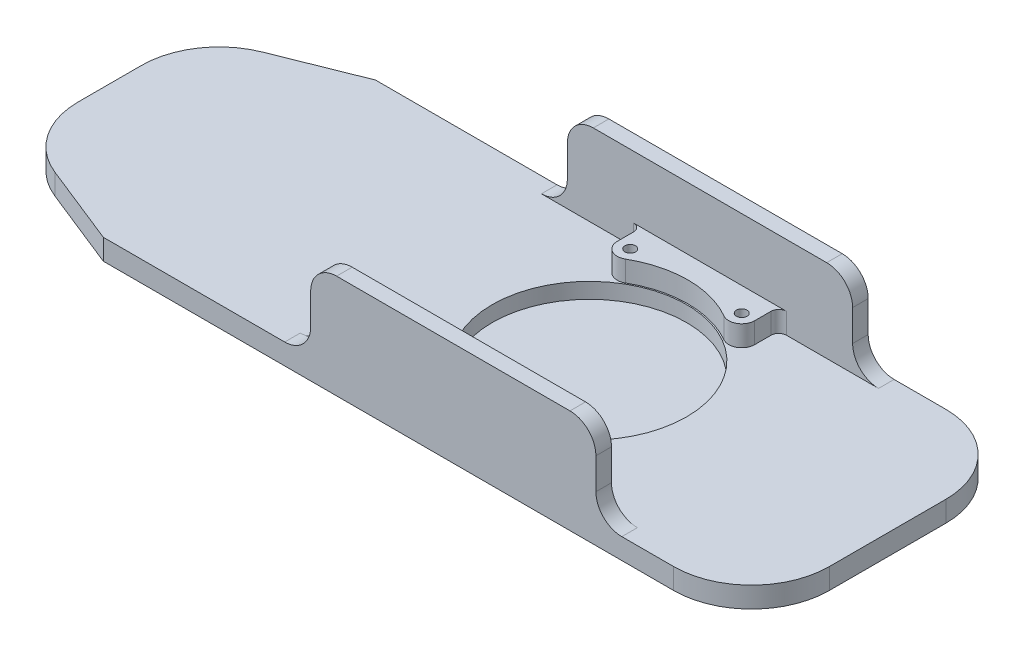
SolidWorks part; units mm, degrees
ref_plane "前视基准面" through (0, 0, 0) normal (0, 0, 1) x (1, 0, 0)
ref_plane "上视基准面" through (0, 0, 0) normal (0, 1, 0) x (1, 0, 0)
ref_plane "右视基准面" through (0, 0, 0) normal (1, 0, 0) x (0, 0, -1)
sketch "草图1" plane through (0, 0, 0) normal (0, 0, 1) x (1, 0, 0)
  line L0 (0, 0) -> (300, 0)
  line L1 (300, 0) -> (300, 40)
  line L2 (300, 40) -> (130, 40)
  line L3 (130, 40) -> (0, 8)
  line L4 (0, 8) -> (0, 0)
  dimension "D1" = 300
  dimension "D2" = 40
  dimension "D3" = 170
  dimension "D4" = 8
extrude "凸台-拉伸1" add sketch "草图1" along normal mid plane 105
sketch "草图3" plane through (0, 40, 0) normal (0, 1, 0) x (1, 0, 0)
  line L0 (300, -52.5) -> (130, -52.5) construction
  line L1 (300, 52.5) -> (240, 52.5)
  line L2 (300, 52.5) -> (300, -52.5)
  line L3 (300, -52.5) -> (240, -52.5)
  line L4 (240, 52.5) -> (240, -52.5)
  dimension "D1" = 60
extrude "切除-拉伸1" cut sketch "草图3" against normal offset from surface (32 mm away) 8 up to face at (150, 0, 0)
ref_plane "基准面4" through (0, 0, 30) normal (0, 0, 1) x (1, 0, 0)
sketch "草图4" plane through (0, 0, 30) normal (0, 0, 1) x (1, 0, 0)
  line L0 (300, 0) -> (300, 8) construction
  line L1 (300, 8) -> (246, 8)
  line L2 (300, 8) -> (300, 79)
  line L3 (300, 79) -> (246, 79)
  line L4 (246, 8) -> (246, 79)
  line L5 (0, 0) -> (300, 0) construction
  circle A0 centre (260, 65) radius 9.5
  dimension "D2" = 19
  dimension "D4" = 14
  dimension "D1" = 40
  dimension "D3" = 65
  dimension "D5" = 14
extrude "凸台-拉伸3" add sketch "草图4" along normal mid plane 45
extrude "切除-拉伸2" cut sketch "草图4<3>" against normal mid plane 29
sketch "草图4<3>" plane through (0, 0, 30) normal (0, 0, 1) x (1, 0, 0) same geometry as "草图4"
sketch "草图5" plane through (0, 0, 44.5) normal (0, 0, -1) x (-1, 0, 0)
  circle A0 centre (-260, 65) radius 9.5
  circle A1 centre (-260, 65) radius 8
  circle A2 centre (-260, 65) radius 9.5 construction
  dimension "D1" = 16
  dimension "D2" = 19
extrude "凸台-拉伸4" add sketch "草图5" against normal blind 2
sketch "草图6" plane through (0, 0, 15.5) normal (0, 0, 1) x (1, 0, 0)
  circle A0 centre (260, 65) radius 8
  circle A1 centre (260, 65) radius 9.5
extrude "凸台-拉伸5" add sketch "草图6" against normal blind 2
fillet "圆角1" radius 14 2 edges at (246, 79, 48.5) (246, 79, 11.5)
mirror "镜向2" about plane through (0, 0, 0) normal (0, 0, 1) of "圆角1", "凸台-拉伸3", "切除-拉伸2", "凸台-拉伸4", "凸台-拉伸5"
sketch "草图8" plane through (0, 0, 0) normal (-1, 0, 0) x (0, 0, 1)
  line L0 (52.5, 8) -> (-52.5, 8) construction
  line L1 (-47.5, 8) -> (47.5, 8)
  line L2 (-47.5, 8) -> (-47.5, 86.9311)
  line L3 (-47.5, 86.9311) -> (47.5, 86.9311)
  line L4 (47.5, 8) -> (47.5, 86.9311)
  line L5 (52.5, 40) -> (52.5, 8) construction
  line L6 (-52.5, 40) -> (-52.5, 8) construction
  dimension "D1" = 5
  dimension "D2" = 5
extrude "切除-拉伸4" cut sketch "草图8" against normal blind 130
sketch "草图7" plane through (0, 0, 0) normal (1, 0, 0) x (0, 0, -1)
  circle A0 centre (0, 65) radius 11
  dimension "D1" = 22
  dimension "D2" = 65
extrude "切除-拉伸3" [suppressed] cut sketch "草图7" along normal up to surface (240 mm away)
sketch "草图10" plane through (0, 40, 0) normal (0, 1, 0) x (1, 0, 0)
  line L0 (130, 47.5) -> (130, -47.5) construction
  line L1 (135, 46.5) -> (235, 46.5)
  line L2 (135, 46.5) -> (135, -46.5)
  line L3 (135, -46.5) -> (235, -46.5)
  line L4 (235, 46.5) -> (235, -46.5)
  line L6 (240, -52.5) -> (130, -52.5) construction
  line L7 (240, 52.5) -> (130, 52.5) construction
  line L8 (240, 52.5) -> (240, -52.5) construction
  dimension "D1" = 5
  dimension "D2" = 5
  dimension "D3" = 6
  dimension "D4" = 6
extrude "切除-拉伸6" cut sketch "草图10" against normal up to surface (32 mm away) up to face at (65, 8, 0)
sketch "草图11" plane through (0, 0, 0) normal (0, -1, 0) x (1, 0, 0)
  line L0 (-14.6132, 52.5) -> (50.0309, 52.5)
  line L1 (130, 52.5) -> (0, 52.5) construction
  line L5 (0, -47.5) -> (0, 47.5) construction
  line L6 (0, 32.5) -> (0, -32.5)
  line L10 (130, -52.5) -> (0, -52.5) construction
  line L11 (50, -52.5) -> (-14.6132, -52.5)
  line L12 (-14.6132, -52.5) -> (-14.6132, 52.5)
  line L14 (0, 32.5) -> (50.0309, 52.5)
  line L15 (0, -32.5) -> (50, -52.5)
  line L16 (0, 52.5) -> (300, 52.5) construction
  dimension "D2" = 20
  dimension "D3" = 20
extrude "切除-拉伸7" cut sketch "草图11" against normal blind 73
sketch "草图12" plane through (0, 8, 0) normal (0, 1, 0) x (1, 0, 0)
  line L1 (50, 52.5) -> (30.577, 52.5)
  line L2 (50, 52.5) -> (50, -69.3601)
  line L3 (50, -69.3601) -> (30.577, -69.3601)
  line L4 (30.577, 52.5) -> (30.577, -69.3601)
extrude "切除-拉伸8" cut sketch "草图12" along normal blind 73
sketch "草图14" plane through (0, 0, 52.5) normal (0, 0, 1) x (1, 0, 0)
  line L0 (300, 79) -> (260, 79) construction
  line L1 (275.0754, 79) -> (318.0378, 79)
  line L2 (318.0378, 79) -> (300, 8)
  arc A0 (275.0754, 79) -> (300, 8) centre (150.7862, -4.5067) cw
extrude "切除-拉伸10" cut sketch "草图14" against normal mid plane 300
sketch "草图15" plane through (0, 8, 0) normal (0, 1, 0) x (1, 0, 0)
  line L0 (185, 0) -> (185, 27.1177) construction
  line L2 (135, 0) -> (219.6534, 0) construction
  line L3 (135, 46.5) -> (135, -46.5) construction
  line L4 (226.5348, 11.1292) -> (185, 0) construction
  line L5 (235, -46.5) -> (235, 46.5) construction
  line L6 (185, 0) -> (163.5, -37.2391) construction
  line L7 (185, 0) -> (147.7609, -21.5) construction
  circle A0 centre (185, 0) radius 43 construction
  circle A3 centre (163.5, -37.2391) radius 2.05
  circle A5 centre (185, 0) radius 43 construction
  circle A8 centre (185, 0) radius 43 construction
  circle A13 centre (163.5, 37.2391) radius 2.05
  circle A15 centre (206.5, 37.2391) radius 2.05
  circle A17 centre (206.5, -37.2391) radius 2.05
  circle A19 centre (185, 0) radius 37.5
  point P28 (185, 0)
  dimension "D2" = 150
  dimension "D3" = 86
  dimension "D7" = 75
  dimension "D8" = 4.1
  dimension "D1" = 15
  dimension "D5" = 50
  dimension "D6" = 30
  dimension "D4" = 3
extrude "切除-拉伸11" cut sketch "草图15" against normal through all
chamfer "倒角1" [suppressed] distance 2.5 angle 45
sketch "草图16" plane through (0, 0, 52.5) normal (0, 0, 1) x (1, 0, 0)
  line L0 (240, 40) -> (130, 40) construction
  line L1 (140, 40) -> (230, 40)
  line L2 (140, 40) -> (140, 25)
  line L3 (140, 25) -> (230, 25)
  line L4 (230, 40) -> (230, 25)
  dimension "D1" = 10
  dimension "D2" = 10
  dimension "D3" = 15
extrude "切除-拉伸12" [suppressed] cut sketch "草图16" against normal through all
chamfer "倒角2" [suppressed] distance 2.5 angle 45
sketch "草图18" plane through (0, 0, 52.5) normal (0, 0, 1) x (1, 0, 0)
  line L1 (246, 8) -> (307.2222, 8)
  line L2 (246, 8) -> (246, 105.8082)
  line L3 (246, 105.8082) -> (307.2222, 105.8082)
  line L4 (307.2222, 8) -> (307.2222, 105.8082)
extrude "切除-拉伸13" cut sketch "草图18" against normal blind 170
sketch "草图19" plane through (0, 0, 0) normal (0, -1, 0) x (1, 0, 0)
  circle A0 centre (185, 0) radius 37.5
extrude "凸台-拉伸6" add sketch "草图19" against normal blind 2
fillet "圆角2" radius 30 4 edges at (0, 4, -32.5) (0, 4, 32.5) (300, 4, -52.5) (300, 4, 52.5)
sketch "草图21" plane through (0, 8, 0) normal (0, 1, 0) x (1, 0, 0)
  line L1 (130, 52.5) -> (-2.1093, 52.5)
  line L2 (130, 52.5) -> (130, -73.0189)
  line L3 (130, -73.0189) -> (-2.1093, -73.0189)
  line L4 (-2.1093, 52.5) -> (-2.1093, -73.0189)
extrude "切除-拉伸15" cut sketch "草图21" along normal blind 149
hole_wizard "大小mm 暗销孔1" positions "3D草图1" profile "草图22" hole size "Ø10.0" standard "GB"
sketch3d "3D草图1"
  line L0 (163.5, 0, 37.2391) -> (163.5, 8, 37.2391) construction
  line L1 (206.5, 0, 37.2391) -> (206.5, 8, 37.2391) construction
  line L2 (206.5, 0, -37.2391) -> (206.5, 8, -37.2391) construction
  line L3 (163.5, 0, -37.2391) -> (163.5, 8, -37.2391) construction
  point P0 (163.5, 0, 37.2391)
  point P4 (206.5, 0, 37.2391)
  point P8 (206.5, 0, -37.2391)
  point P12 (163.5, 0, -37.2391)
sketch "草图22" plane through (163.5, 0, 37.2391) normal (1, 0, 0) x (0, 0, -1)
  line L0 (0, 0) -> (0, 7.0043)
  line L1 (0, 7.0043) -> (5, 4)
  line L2 (5, 4) -> (5, 0)
  line L5 (5, 0) -> (0, 0)
  line L10 (0, 7.0043) -> (-5, 4) construction
  line L11 (0, -6.35) -> (0, 107.95) construction
  dimension "孔直径" = 10
  dimension "孔深度" = 4
  dimension "导头角度" = 118
sketch "草图23" plane through (130, 0, 0) normal (-1, 0, 0) x (0, 0, 1)
  line L0 (52.5, 40) -> (-52.5, 40) construction
  line L1 (-46.5, 40) -> (46.5, 40)
  line L2 (-46.5, 40) -> (-46.5, 8)
  line L3 (-46.5, 8) -> (46.5, 8)
  line L4 (46.5, 40) -> (46.5, 8)
  line L5 (-52.5, 8) -> (52.5, 8) construction
  line L6 (52.5, 40) -> (52.5, 8) construction
  line L7 (-52.5, 40) -> (-52.5, 8) construction
  dimension "D1" = 6
  dimension "D2" = 6
extrude "切除-拉伸16" cut sketch "草图23" against normal blind 149
sketch "草图24" plane through (0, 8, 0) normal (0, 1, 0) x (1, 0, 0)
  line L0 (130, -46.5) -> (240, -46.5) construction
  line L1 (217.5, 46.5) -> (152.5, 46.5)
  line L2 (217.5, 46.5) -> (217.5, 25)
  line L3 (217.5, -46.5) -> (152.5, -46.5)
  line L4 (152.5, 46.5) -> (152.5, 25)
  line L5 (217.5, 46.5) -> (152.5, -46.5) construction
  line L6 (217.5, -46.5) -> (152.5, 46.5) construction
  line L7 (152.5, -25) -> (152.5, -46.5)
  line L8 (217.5, -25) -> (217.5, -46.5)
  line L9 (152.5, 25) -> (157.0492, 25)
  line L10 (212.9508, 25) -> (217.5, 25)
  line L11 (152.5, -25) -> (157.0492, -25)
  line L12 (212.9508, -25) -> (217.5, -25)
  circle A0 centre (163.5, 37.2391) radius 2.05 construction
  circle A1 centre (163.5, -37.2391) radius 2.05 construction
  circle A2 centre (206.5, -37.2391) radius 2.05 construction
  circle A3 centre (206.5, 37.2391) radius 2.05 construction
  circle A4 centre (185, 0) radius 37.5 construction
  circle A5 centre (163.5, 37.2391) radius 2.05
  circle A6 centre (163.5, -37.2391) radius 2.05
  circle A7 centre (206.5, -37.2391) radius 2.05
  circle A8 centre (206.5, 37.2391) radius 2.05
  arc A9 (157.0492, -25) -> (212.9508, -25) centre (185, 0) ccw
  arc A10 (212.9508, 25) -> (157.0492, 25) centre (185, 0) ccw
  dimension "D1" = 65
  dimension "D2" = 25
  dimension "D3" = 25
extrude "凸台-拉伸7" [suppressed] add sketch "草图24" along normal blind 10
sketch "草图25" plane through (0, 0, -52.5) normal (0, 0, -1) x (-1, 0, 0)
  line L0 (-50, 0) -> (-270, 0) construction
  line L1 (-215, 0) -> (-155, 0)
  line L2 (-215, 0) -> (-215, 13)
  line L3 (-215, 13) -> (-155, 13)
  line L4 (-155, 0) -> (-155, 13)
  point P6 (-185, 0)
  dimension "D1" = 185
  dimension "D2" = 60
  dimension "D3" = 13
extrude "切除-拉伸17" [suppressed] cut sketch "草图25" against normal blind 13
fillet "圆角3" radius 10 8 edges at (240, 8, 49.5) (240, 40, 49.5) (130, 8, 49.5) (130, 40, 49.5) (130, 8, -49.5) (240, 8, -49.5) (240, 40, -49.5) (130, 40, -49.5)
sketch "草图26" plane through (0, 8, 0) normal (0, 1, 0) x (1, 0, 0)
  line L0 (0, 0.0023) -> (404.6786, 0.0023) construction
  line L1 (0, 12.189) -> (0, -12.1843) construction
  line L2 (158.5, 46.5) -> (158.5, 37.2391)
  line L3 (250, 46.5) -> (120, 46.5) construction
  line L4 (185, 82.4708) -> (185, 0) construction
  line L5 (211.5, 46.5) -> (211.5, 37.2391)
  line L8 (211.5, -46.4953) -> (211.5, -37.2344)
  line L9 (158.5, -46.4953) -> (158.5, -37.2344)
  line L10 (158.5, 46.5) -> (158.5, 50.5)
  line L11 (158.5, 50.5) -> (211.5, 50.5)
  line L12 (211.5, 50.5) -> (211.5, 46.5)
  line L13 (230, 46.5) -> (140, 46.5) construction
  line L14 (211.5, -50.4953) -> (211.5, -46.4953)
  line L15 (158.5, -50.4953) -> (211.5, -50.4953)
  line L16 (158.5, -46.4953) -> (158.5, -50.4953)
  arc A3 (158.5, 37.2391) -> (166, 32.909) centre (163.5, 37.2391) ccw
  arc A4 (211.5, 37.2391) -> (204, 32.909) centre (206.5, 37.2391) cw
  arc A6 (204, 32.909) -> (166, 32.909) centre (185, 0) ccw
  arc A7 (204, -32.9043) -> (166, -32.9043) centre (185, 0.0047) cw
  arc A8 (211.5, -37.2344) -> (204, -32.9043) centre (206.5, -37.2344) ccw
  arc A9 (158.5, -37.2344) -> (166, -32.9043) centre (163.5, -37.2344) cw
  dimension "D1" = 10
  dimension "D2" = 4
extrude "凸台-拉伸8" add sketch "草图26" along normal blind 8
sketch "草图27" plane through (0, 0, 0) normal (0, -1, 0) x (1, 0, 0)
  circle A0 centre (206.5, -37.2391) radius 2.05 construction
  circle A1 centre (163.5, -37.2391) radius 2.05 construction
  circle A2 centre (163.5, 37.2391) radius 2.05 construction
  circle A3 centre (206.5, 37.2391) radius 2.05 construction
  circle A4 centre (206.5, -37.2391) radius 2.05
  circle A5 centre (163.5, -37.2391) radius 2.05
  circle A6 centre (163.5, 37.2391) radius 2.05
  circle A7 centre (206.5, 37.2391) radius 2.05
extrude "切除-拉伸18" cut sketch "草图27" against normal blind 47
fillet "圆角4" radius 3 4 edges at (211.5, 12, 46.5) (158.5, 12, 46.5) (158.5, 12, -46.5) (211.5, 12, -46.5)
